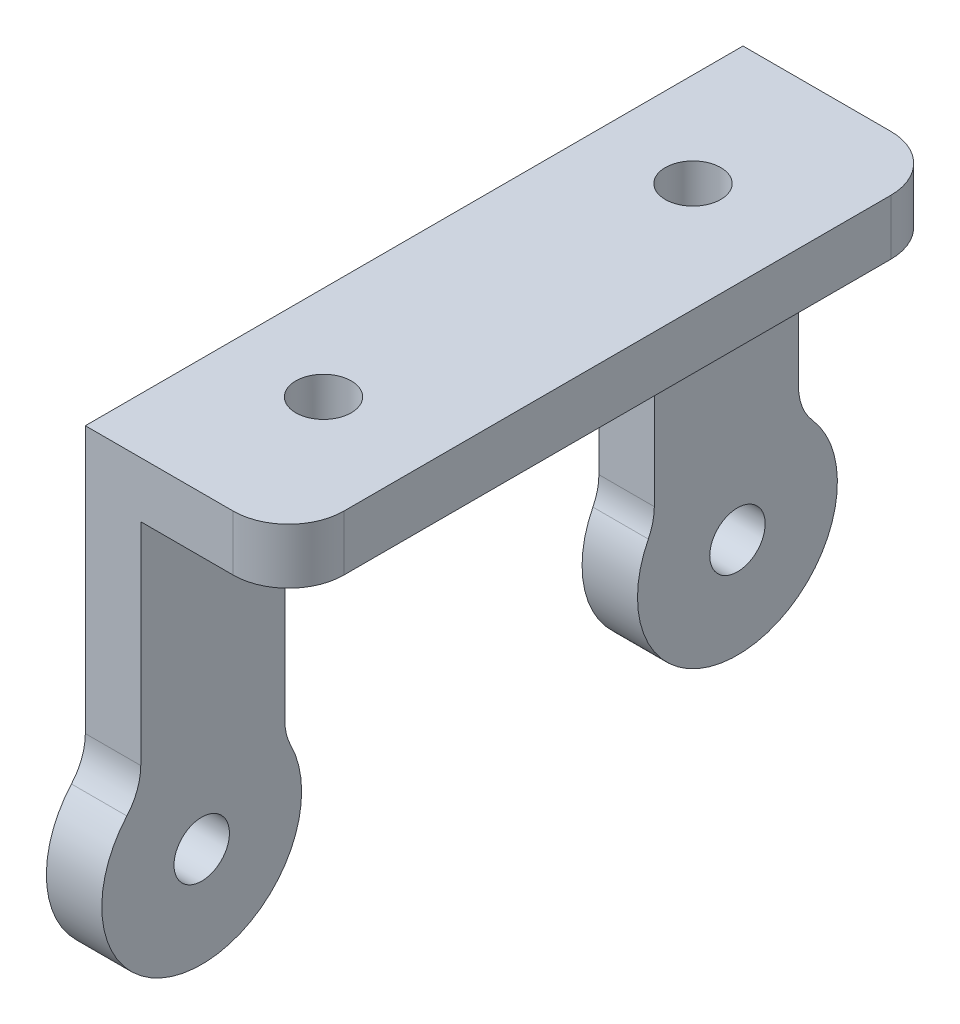
SolidWorks part; units mm, degrees
ref_plane "前视基准面" through (0, 0, 0) normal (0, 0, 1) x (1, 0, 0)
ref_plane "上视基准面" through (0, 0, 0) normal (0, 1, 0) x (1, 0, 0)
ref_plane "右视基准面" through (0, 0, 0) normal (1, 0, 0) x (0, 0, -1)
other "Configuration Table"
sketch "草图1" plane through (0, 0, 0) normal (0, 0, 1) x (1, 0, 0)
  line L0 (-59.8031, 0) -> (83.0494, 0) construction
  line L1 (0, 51.931) -> (0, -59.8013) construction
  line L2 (0, 0) -> (3, 0)
  line L3 (3, 0) -> (3, 35)
  line L4 (3, 35) -> (11, 35)
  line L5 (11, 35) -> (11, 38)
  line L6 (11, 38) -> (0, 38)
  line L7 (0, 38) -> (0, 0)
  dimension "D1" = 3
  dimension "D2" = 35
  dimension "D3" = 8
  dimension "D4" = 3
extrude "凸台-拉伸1" add sketch "草图1" along normal blind 35.6
sketch "草图3" plane through (0, 0, 0) normal (-1, 0, 0) x (0, 0, 1)
  line L0 (17.8, 38) -> (17.8, -9.9451) construction
  line L1 (35.6, 38) -> (0, 38) construction
  line L2 (27.8, 0) -> (7.8, 0)
  line L3 (35.6, 0) -> (0, 0) construction
  line L4 (7.8, 0) -> (7.8, 35)
  line L5 (7.8, 35) -> (27.8, 35)
  line L6 (27.8, 0) -> (27.8, 35)
  circle A0 centre (3.3, 3) radius 1.5
  circle A1 centre (32.3, 3) radius 1.5
  point P12 (17.8, 0)
  point P13 (17.8, 35)
  dimension "D3" = 14.5
  dimension "D1" = 10
  dimension "D2" = 35
  dimension "D4" = 3
extrude "切除-拉伸1" cut sketch "草图3" against normal through all
sketch "草图4" plane through (0, 38, 0) normal (0, 1, 0) x (1, 0, 0)
  line L0 (11, -17.8) -> (-14.7699, -17.8) construction
  line L1 (11, -35.6) -> (11, 0) construction
  circle A0 centre (5.0941, -7.8) radius 1.5
  circle A1 centre (5.0941, -27.8) radius 1.5
  dimension "D1" = 3
  dimension "D2" = 10
extrude "切除-拉伸2" cut sketch "草图4" against normal through all
sketch "草图5" plane through (0, 38, 0) normal (0, 1, 0) x (1, 0, 0)
  line L0 (0, -17.8) -> (31.647, -17.8) construction
  line L1 (0, -35.6) -> (0, 0) construction
fillet "圆角1" radius 3 2 edges at (11, 36.5, 0) (11, 36.5, 35.6)
sketch "草图6" plane through (0, 0, 0) normal (-1, 0, 0) x (0, 0, 1)
  circle A0 centre (3.3, 3) radius 5.41
  circle A1 centre (32.3, 3) radius 5.4083
  circle A2 centre (3.3, 3) radius 1.5
  circle A3 centre (32.3, 3) radius 1.5
  dimension "D1" = 10.82
extrude "凸台-拉伸2" add sketch "草图6" against normal blind 3
fillet "圆角2" radius 3 4 edges at (1.5, 6, 27.8) (1.5, 7.2849, 35.6) (1.5, 6.003, 7.8) (1.5, 7.287, 0)
sketch "草图7" plane through (0, 0, 35.6) normal (0, 0, 1) x (1, 0, 0)
  line L0 (0, 38) -> (0, 8.5687) construction
  line L1 (0, 32.9171) -> (3, 32.9171)
  line L2 (0, 32.9171) -> (0, 17.9171)
  line L3 (0, 17.9171) -> (3, 17.9171)
  line L4 (3, 32.9171) -> (3, 17.9171)
  line L5 (3, 8.5687) -> (3, 35) construction
extrude "切除-拉伸3" cut sketch "草图7" against normal blind 59
move or copy body "实体-移动/复制1" bodies to move or copy 114 copy no translate (0, -15, 0) parameters "D1"=0, "D2"=15, "D3"=0
combine bodies "组合3" operation type add bodies to combine 120 115 116
